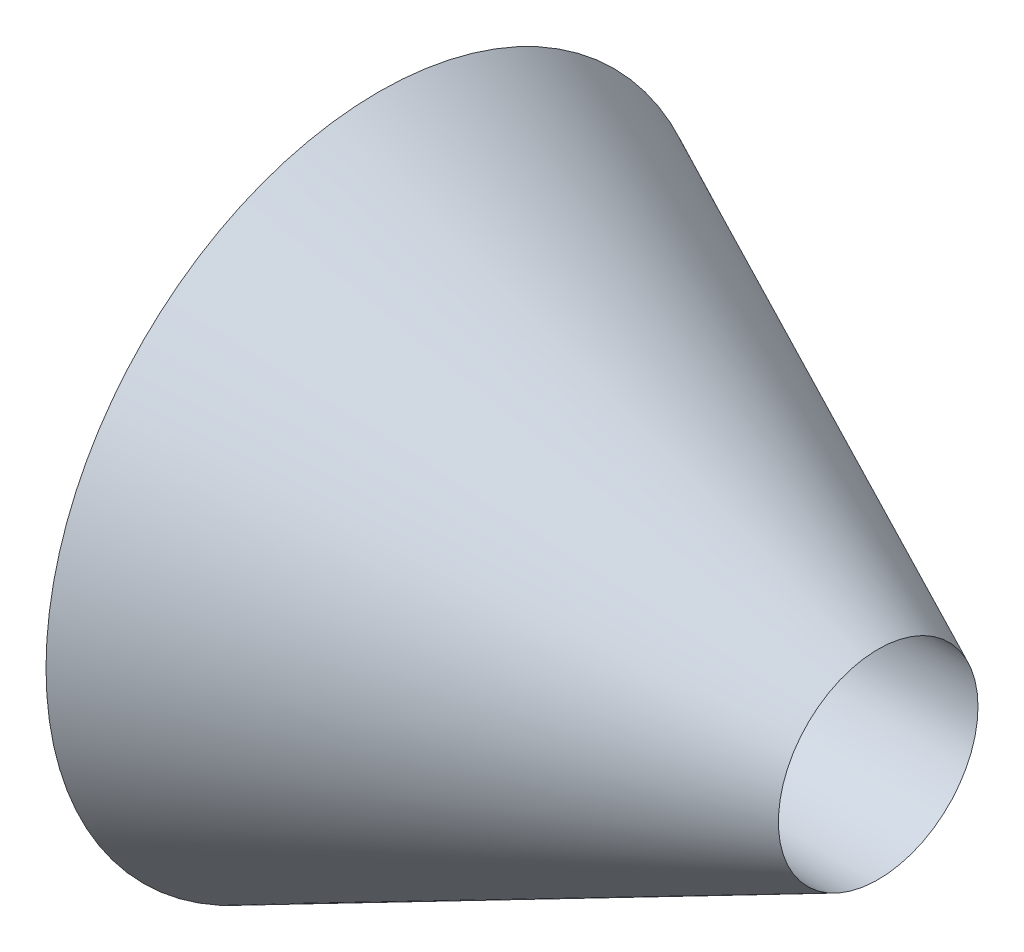
SolidWorks part; units mm, degrees
ref_plane "Front Plane" through (0, 0, 0) normal (0, 0, 1) x (1, 0, 0)
ref_plane "Top Plane" through (0, 0, 0) normal (0, 1, 0) x (1, 0, 0)
ref_plane "Right Plane" through (0, 0, 0) normal (1, 0, 0) x (0, 0, -1)
sketch "Sketch1" plane through (0, 0, 0) normal (1, 0, 0) x (0, 0, -1)
  circle A0 centre (0, 0) radius 1.5
  circle A1 centre (0, 0) radius 5
  dimension "D1" = 3
  dimension "D2" = 10
extrude "Boss-Extrude1" add sketch "Sketch1" along normal blind 15 draft 25 contours A0 | A1 A0 region at (0, 0, 0) region at (0, 0, 4.8586)
extrude "Cut-Extrude1" cut sketch "Sketch1<4>" along normal blind 15 contours A0
sketch "Sketch1<4>" plane through (0, 0, 0) normal (1, 0, 0) x (0, 0, -1) same geometry as "Sketch1"
